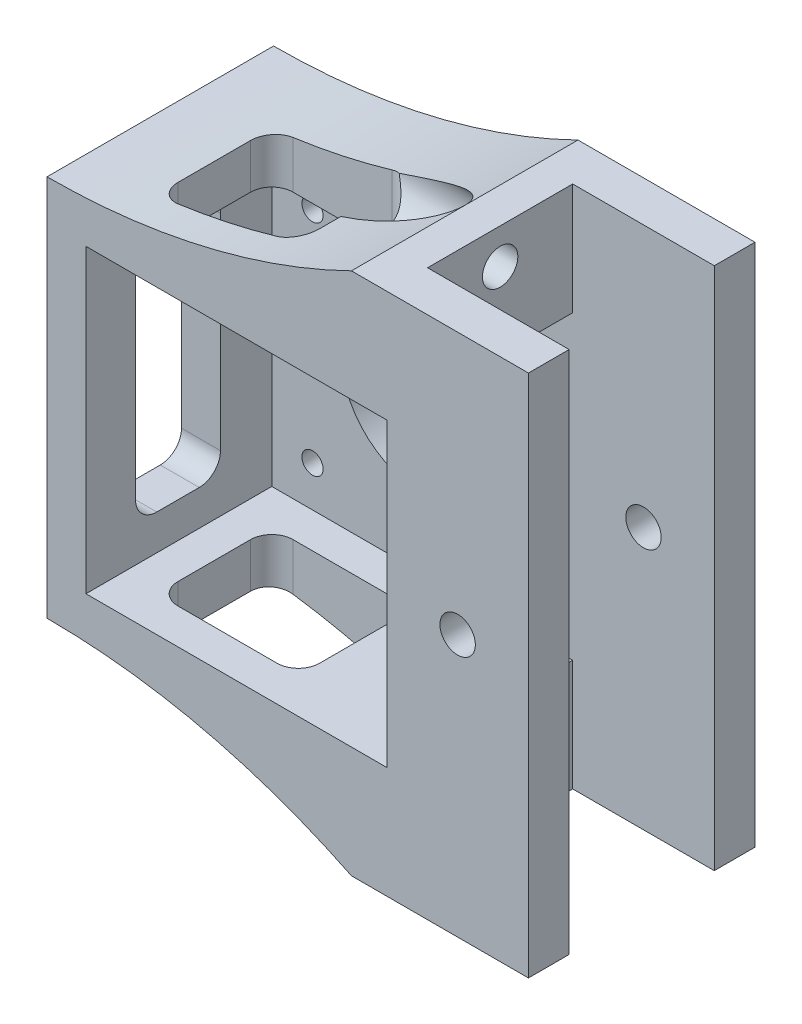
SolidWorks part; units mm, degrees
material "PBT Общее назначение"
ref_plane "Спереди" through (0, 0, 0) normal (0, 0, 1) x (1, 0, 0)
ref_plane "Сверху" through (0, 0, 0) normal (0, 1, 0) x (1, 0, 0)
ref_plane "Справа" through (0, 0, 0) normal (1, 0, 0) x (0, 0, -1)
sketch "Эскиз1" plane through (0, 0, 0) normal (0, 0, 1) x (1, 0, 0)
  line L0 (0, -37) -> (0, 37)
  line L1 (0, 37) -> (25, 37)
  line L2 (0, -37) -> (25, -37)
  line L3 (68, 27) -> (0, 27) construction
  line L4 (68, 27) -> (68, -27)
  line L5 (0, 0) -> (68, 0) construction
  arc A0 (25, 37) -> (68, 27) centre (68, 124.45) ccw
  arc A1 (25, -37) -> (68, -27) centre (68, -124.45) cw
  dimension "D1" = 37
  dimension "D2" = 68
  dimension "D3" = 25
  dimension "D4" = 27
  dimension "D5" = 43
extrude "Бобышка-Вытянуть1" add sketch "Эскиз1" along normal blind 52
sketch "Эскиз2" plane through (0, 0, 52) normal (0, 0, 1) x (1, 0, 0)
  line L0 (68, 0) -> (-10.2579, 0) construction
  line L1 (68, -27) -> (68, 27) construction
  line L2 (62.5, 21.25) -> (62.5, -21.25)
  line L3 (62.5, 21.25) -> (20, 21.25)
  line L4 (62.5, -21.25) -> (20, -21.25)
  line L5 (20, 21.25) -> (20, -21.25)
  line L6 (68, 0) -> (20, 0) construction
  line L7 (0, 37) -> (0, -37) construction
  dimension "D1" = 42.5
  dimension "D2" = 20
  dimension "D3" = 42.5
extrude "Вырез-Вытянуть1" cut sketch "Эскиз2" against normal through all
sketch "Эскиз3" plane through (0, 0, 0) normal (-1, 0, 0) x (0, 0, 1)
  line L0 (26, 37) -> (26, -37) construction
  line L1 (52, 37) -> (0, 37) construction
  line L2 (52, -37) -> (0, -37) construction
  line L3 (15.75, 37) -> (36.25, 37)
  line L4 (15.75, 37) -> (15.75, -37)
  line L5 (36.25, 37) -> (36.25, -37)
  line L6 (15.75, -37) -> (36.25, -37)
  line L7 (26, -37) -> (26, 37) construction
  dimension "D1" = 20.5
extrude "Вырез-Вытянуть2" cut sketch "Эскиз3" against normal blind 20
sketch "Эскиз4" plane through (0, 0, 0) normal (0, 0, -1) x (-1, 0, 0)
  line L4 (0, 37) -> (-25, 37)
  line L5 (-68, 27) -> (-68, -27)
  line L6 (-25, -37) -> (0, -37)
  line L7 (0, -37) -> (0, 37)
  line L8 (0, 37) -> (-25, 37)
  line L9 (-68, 27) -> (-68, -27)
  line L10 (-25, -37) -> (0, -37)
  line L11 (0, -37) -> (0, 37)
  arc A2 (-68, 27) -> (-25, 37) centre (-68, 124.45) ccw
  arc A3 (-25, -37) -> (-68, -27) centre (-68, -124.45) ccw
  arc A4 (-68, 27) -> (-25, 37) centre (-68, 124.45) ccw
  arc A5 (-25, -37) -> (-68, -27) centre (-68, -124.45) ccw
  dimension "D1" = 0
extrude "Вырез-Вытянуть3" cut sketch "Эскиз4" against normal blind 10
sketch "Эскиз5" plane through (0, 0, 52) normal (0, 0, 1) x (1, 0, 0)
  line L4 (25, 37) -> (0, 37)
  line L5 (0, 37) -> (0, -37)
  line L6 (0, -37) -> (25, -37)
  line L7 (68, -27) -> (68, 27)
  line L8 (25, 37) -> (0, 37)
  line L9 (0, 37) -> (0, -37)
  line L10 (0, -37) -> (25, -37)
  line L11 (68, -27) -> (68, 27)
  arc A2 (68, -27) -> (25, -37) centre (68, -124.45) ccw
  arc A3 (25, 37) -> (68, 27) centre (68, 124.45) ccw
  arc A4 (68, -27) -> (25, -37) centre (68, -124.45) ccw
  arc A5 (25, 37) -> (68, 27) centre (68, 124.45) ccw
  dimension "D1" = 0
extrude "Вырез-Вытянуть4" cut sketch "Эскиз5" against normal blind 10
sketch "Эскиз6" plane through (0, 0, 10) normal (0, 0, -1) x (-1, 0, 0)
  line L0 (-20, -21.25) -> (-62.5, -21.25) construction
  line L1 (-20, 21.25) -> (-20, -21.25) construction
  line L2 (-62.5, 21.25) -> (-20, 21.25) construction
  line L3 (-62.5, -21.25) -> (-62.5, 21.25) construction
  line L4 (-20, -21.25) -> (-62.5, -21.25)
  line L5 (-20, 21.25) -> (-20, -21.25)
  line L6 (-62.5, 21.25) -> (-20, 21.25)
  line L7 (-62.5, -21.25) -> (-62.5, 21.25)
extrude "Бобышка-Вытянуть2" add sketch "Эскиз6" against normal up to surface (5.75 mm away) up to face at (13.3333, 0, 15.75)
sketch "Эскиз7" plane through (0, 0, 15.75) normal (0, 0, 1) x (1, 0, 0)
  line L0 (20, -21.25) -> (20, 21.25) construction
  line L1 (62.5, -21.25) -> (20, -21.25) construction
  line L2 (62.5, 21.25) -> (62.5, -21.25) construction
  line L3 (20, 21.25) -> (62.5, 21.25) construction
  line L4 (20, -21.25) -> (20, 21.25) construction
  line L5 (62.5, -21.25) -> (20, -21.25) construction
  line L6 (62.5, 21.25) -> (62.5, -21.25) construction
  line L7 (20, 21.25) -> (62.5, 21.25) construction
  line L8 (41.25, -21.25) -> (41.25, 21.25) construction
  line L9 (20, 0) -> (62.5, 0) construction
  circle A0 centre (41.25, 0) radius 11.5
  dimension "D1" = 23
extrude "Вырез-Вытянуть5" cut sketch "Эскиз7" against normal through all
sketch "Эскиз8" plane through (20, 0, 0) normal (-1, 0, 0) x (0, 0, 1)
  line L0 (42, -27) -> (10, -27) construction
  line L1 (36.25, -27) -> (15.75, -27) construction
  line L2 (15.75, -37) -> (36.25, -37) construction
  line L3 (15.75, -37) -> (36.25, -37) construction
  line L4 (15.75, -21.25) -> (15.75, -37) construction
  line L5 (36.25, -37) -> (36.25, -21.25) construction
  line L6 (15.75, -27) -> (15.75, -37) construction
  line L7 (36.25, -37) -> (36.25, -27) construction
  line L8 (26, -37) -> (26, -27) construction
  line L9 (36.25, -32) -> (15.75, -32) construction
  line L10 (36.25, 37) -> (15.75, 37) construction
  line L12 (15.75, 37) -> (15.75, 21.25) construction
  line L13 (36.25, 21.25) -> (36.25, 37) construction
  line L14 (36.25, 37) -> (15.75, 37) construction
  line L15 (26, 27) -> (26, 37) construction
  line L16 (15.75, 37) -> (15.75, 27) construction
  line L17 (36.25, 27) -> (36.25, 37) construction
  line L18 (42, 27) -> (10, 27) construction
  line L19 (36.25, 27) -> (15.75, 27) construction
  line L20 (15.75, 32) -> (36.25, 32) construction
  circle A0 centre (26, -32) radius 2.5
  circle A1 centre (26, 32) radius 2.5
  dimension "D1" = 5
  dimension "D2" = 5
extrude "Вырез-Вытянуть6" cut sketch "Эскиз8" against normal through all
sketch "Эскиз9" plane through (0, 0, 10) normal (0, 0, -1) x (-1, 0, 0)
  line L0 (-68, 0) -> (0, 0) construction
  line L1 (-68, 27) -> (-68, -27) construction
  line L2 (0, -37) -> (0, 37) construction
ref_plane "СимY" through (0, 0, 0) normal (0, -1, 0) x (-1, 0, 0)
ref_plane "Плоскость2" through (25, 0, 0) normal (-1, 0, 0) x (0, 0, 1)
sketch "Эскиз10" plane through (25, 0, 0) normal (-1, 0, 0) x (0, 0, 1)
  circle A0 centre (26, 32) radius 2.5 construction
  circle A1 centre (26, -32) radius 2.5 construction
  circle A2 centre (26, 32) radius 2.5 construction
  circle A3 centre (26, -32) radius 2.5 construction
  circle A4 centre (26, 32) radius 5
  circle A5 centre (26, -32) radius 5
  dimension "D1" = 10
  dimension "D2" = 10
extrude "Вырез-Вытянуть7" cut sketch "Эскиз10" against normal through all
sketch "Эскиз12" plane through (0, 0, 10) normal (0, 0, -1) x (-1, 0, 0)
  line L0 (-20, 37) -> (0, 37) construction
  line L1 (0, 37) -> (0, -37) construction
  line L2 (-20, -37) -> (0, -37) construction
  line L3 (-20, 37) -> (0, 37) construction
  line L4 (0, 37) -> (0, -37) construction
  line L5 (-20, -37) -> (0, -37) construction
  line L6 (-20, 37) -> (-20, 21.25) construction
  line L7 (-20, 37) -> (-20, -37) construction
  line L8 (-20, 0) -> (0, 0) construction
  line L9 (-10, 37) -> (-10, -37) construction
  circle A0 centre (-10, 0) radius 2.5
  dimension "D1" = 5
extrude "Вырез-Вытянуть8" cut sketch "Эскиз12" against normal through all
sketch "Эскиз13" plane through (68, 0, 0) normal (1, 0, 0) x (0, 0, -1)
  line L0 (-42, 0) -> (-10, 0) construction
  line L1 (-42, -27) -> (-42, 27) construction
  line L2 (-26, 0) -> (-26, -36.6008) construction
  line L3 (-26, -27) -> (-10, -27) construction
ref_plane "СимZ" through (0, 0, 26) normal (0, 0, 1) x (0, -1, 0)
sketch "Эскиз14" plane through (0, 0, 10) normal (0, 0, -1) x (-1, 0, 0)
  line L0 (-41.25, 0) -> (-41.25, 11.5) construction
  line L1 (-41.25, 0) -> (-29.75, 0) construction
  line L2 (-56.75, 15.5) -> (-25.75, 15.5) construction
  line L3 (-56.75, 15.5) -> (-56.75, -15.5) construction
  line L4 (-25.75, 15.5) -> (-25.75, -15.5) construction
  line L5 (-56.75, -15.5) -> (-25.75, -15.5) construction
  line L6 (-41.25, 15.5) -> (-41.25, -15.5) construction
  line L7 (-25.75, 0) -> (-56.75, 0) construction
  circle A0 centre (-41.25, 0) radius 11.5 construction
  circle A1 centre (-41.25, 0) radius 11.5 construction
  circle A2 centre (-56.75, 15.5) radius 1.5
  circle A3 centre (-25.75, 15.5) radius 1.5
  circle A4 centre (-25.75, -15.5) radius 1.5
  circle A5 centre (-56.75, -15.5) radius 1.5
  dimension "D3" = 3
  dimension "D4" = 3
  dimension "D5" = 3
  dimension "D6" = 3
  dimension "D1" = 31
  dimension "D2" = 31
extrude "Вырез-Вытянуть9" cut sketch "Эскиз14" against normal up to surface (5.75 mm away) up to face at (10, 2.5, 15.75)
sketch "Эскиз15" plane through (68, 0, 0) normal (1, 0, 0) x (0, 0, -1)
  line L0 (-35, 18.75) -> (-23, 18.75)
  line L1 (-35, 18.75) -> (-35, -16.25)
  line L2 (-23, 18.75) -> (-23, -16.25)
  line L3 (-35, -16.25) -> (-23, -16.25)
  line L4 (-10, 27) -> (-10, -27) construction
  line L5 (-42, -27) -> (-42, 27) construction
  line L7 (-15.75, -21.25) -> (-42, -21.25) construction
  line L8 (-15.75, 21.25) -> (-42, 21.25) construction
  line L9 (-15.75, -21.25) -> (-42, -21.25) construction
  line L10 (-15.75, 21.25) -> (-42, 21.25) construction
  dimension "D1" = 12
  dimension "D2" = 13
  dimension "D3" = 7
  dimension "D4" = 5
  dimension "D5" = 5
extrude "Вырез-Вытянуть10" cut sketch "Эскиз15" against normal up to surface (5.5 mm away) up to face at (62.5, 0, 28.875)
ref_plane "Зеркало" through (0, 0, 0) normal (-1, 0, 0) x (0, 0, 1)
sketch "Sketch1" plane through (0, -21.25, 0) normal (0, 1, 0) x (1, 0, 0)
  line L0 (57.5, -20.75) -> (37.5, -20.75)
  line L1 (57.5, -20.75) -> (57.5, -37)
  line L2 (37.5, -20.75) -> (37.5, -37)
  line L3 (57.5, -37) -> (37.5, -37)
  line L4 (62.5, -15.75) -> (62.5, -42) construction
  line L5 (62.5, -42) -> (20, -42) construction
  line L6 (20, -15.75) -> (62.5, -15.75) construction
  dimension "D1" = 5
  dimension "D2" = 5
  dimension "D3" = 5
  dimension "D4" = 20
extrude "Cut-Extrude1" cut sketch "Sketch1" against normal through all and the other way through all
sketch "Sketch2" plane through (0, 0, 42) normal (0, 0, 1) x (1, 0, 0)
  line L0 (57.5, 21.25) -> (57.5, 27.5673) construction
  line L1 (57.5, 21.25) -> (57.5, 27.5673)
  line L2 (20, 21.25) -> (62.5, 21.25) construction
  line L3 (57.5, 21.25) -> (68, 21.25)
  line L4 (68, -27) -> (68, 27) construction
  line L5 (68, 21.25) -> (68, 27)
  arc A0 (25, 37) -> (68, 27) centre (68, 124.45) ccw construction
  arc A1 (57.5, 27.5673) -> (68, 27) centre (68, 124.45) ccw
extrude "Boss-Extrude1" add sketch "Sketch2" against normal through all
mirror "Mirror1" about plane through (0, 0, 0) normal (0, -1, 0) of "Boss-Extrude1"
mirror "Зеркальное отражение1" about plane through (0, 0, 0) normal (-1, 0, 0) of bodies 146 142
delete or keep bodies "Body-Delete/Keep 2" type delete bodies bodies 146
fillet "Fillet19" radius 3 12 edges at (-57.5, -24.4087, 20.75) (-57.5, -24.4087, 37) (-57.5, 24.4087, 20.75) (-57.5, 24.4087, 37) (-65.25, -16.25, 35) (-65.25, -16.25, 23) (-65.25, 18.75, 23) (-65.25, 18.75, 35) (-37.5, 26.573, 37) (-37.5, 26.573, 20.75) (-37.5, -26.573, 37) (-37.5, -26.573, 20.75)
